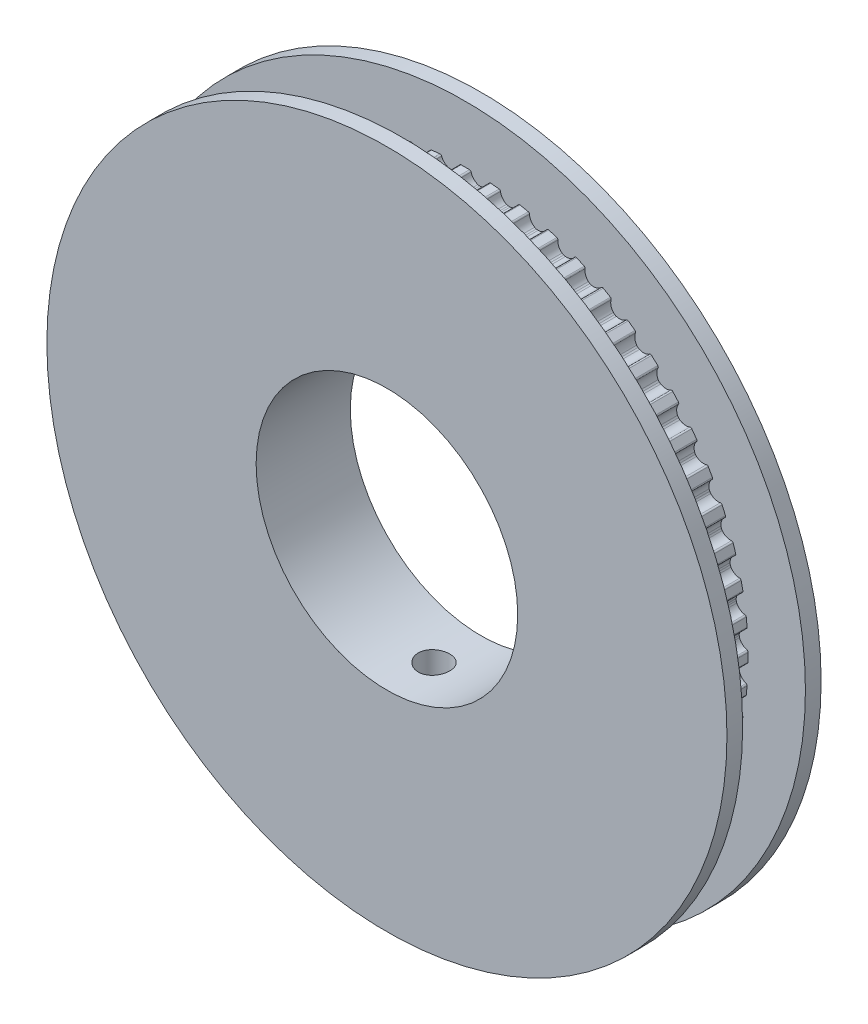
SolidWorks part; units mm, degrees
ref_plane "Front Plane" through (0, 0, 0) normal (0, 0, 1) x (1, 0, 0)
ref_plane "Top Plane" through (0, 0, 0) normal (0, 1, 0) x (1, 0, 0)
ref_plane "Right Plane" through (0, 0, 0) normal (1, 0, 0) x (0, 0, -1)
sketch "Sketch2" plane through (0, 0, 0) normal (0, 0, 1) x (1, 0, 0)
  circle A0 centre (0, 0) radius 27.693
  dimension "D1" = 55.3859
extrude "Boss-Extrude1" add sketch "Sketch2" along normal mid plane 6
sketch "Sketch3" plane through (0, 0, 3) normal (0, 0, 1) x (1, 0, 0)
  line L0 (0, 0) -> (0, 27.0327) construction
  line L1 (0, 27.0327) -> (0.4, 27.0327)
  line L4 (0, 0) -> (1.4605, 27.8689) construction
  line L8 (0, 27.0327) -> (0, 27.8689)
  line L9 (0, 27.8689) -> (1.4605, 27.8689)
  line L10 (2.9131, 27.7163) -> (1.4605, 27.8689)
  line L11 (2.8257, 26.8846) -> (2.4279, 26.9264)
  line L12 (2.8257, 26.8846) -> (2.9131, 27.7163)
  line L13 (5.7943, 27.2599) -> (4.3656, 27.5636)
  line L14 (2.9131, 27.7163) -> (4.3656, 27.5636)
  line L15 (2.8257, 26.8846) -> (2.9131, 27.7163)
  line L16 (2.8257, 26.8846) -> (3.2235, 26.8428)
  line L17 (5.6204, 26.442) -> (5.2292, 26.5251)
  line L18 (5.6204, 26.442) -> (5.7943, 27.2599)
  line L19 (8.612, 26.5049) -> (7.2229, 26.9563)
  line L20 (5.7943, 27.2599) -> (7.2229, 26.9563)
  line L21 (5.6204, 26.442) -> (5.7943, 27.2599)
  line L22 (5.6204, 26.442) -> (6.0117, 26.3588)
  line L23 (8.3536, 25.7096) -> (7.9731, 25.8332)
  line L24 (8.3536, 25.7096) -> (8.612, 26.5049)
  line L25 (11.3353, 25.4595) -> (10.001, 26.0536)
  line L26 (8.612, 26.5049) -> (10.001, 26.0536)
  line L27 (8.3536, 25.7096) -> (8.612, 26.5049)
  line L28 (8.3536, 25.7096) -> (8.734, 25.586)
  line L29 (10.9952, 24.6956) -> (10.6298, 24.8583)
  line L30 (10.9952, 24.6956) -> (11.3353, 25.4595)
  line L31 (13.9345, 24.1352) -> (12.6696, 24.8655)
  line L32 (11.3353, 25.4595) -> (12.6696, 24.8655)
  line L33 (10.9952, 24.6956) -> (11.3353, 25.4595)
  line L34 (10.9952, 24.6956) -> (11.3606, 24.5329)
  line L35 (13.5164, 23.411) -> (13.1699, 23.611)
  line L36 (13.5164, 23.411) -> (13.9345, 24.1352)
  line L37 (16.381, 22.5465) -> (15.1993, 23.4049)
  line L38 (13.9345, 24.1352) -> (15.1993, 23.4049)
  line L39 (13.5164, 23.411) -> (13.9345, 24.1352)
  line L40 (13.5164, 23.411) -> (13.8628, 23.211)
  line L41 (15.8894, 21.8699) -> (15.5658, 22.105)
  line L42 (15.8894, 21.8699) -> (16.381, 22.5465)
  line L43 (18.648, 20.7107) -> (17.5626, 21.688)
  line L44 (16.381, 22.5465) -> (17.5626, 21.688)
  line L45 (15.8894, 21.8699) -> (16.381, 22.5465)
  line L46 (15.8894, 21.8699) -> (16.213, 21.6348)
  line L47 (18.0884, 20.0892) -> (17.7911, 20.3569)
  line L48 (18.0884, 20.0892) -> (18.648, 20.7107)
  line L49 (20.7107, 18.648) -> (19.7334, 19.7334)
  line L50 (18.648, 20.7107) -> (19.7334, 19.7334)
  line L51 (18.0884, 20.0892) -> (18.648, 20.7107)
  line L52 (18.0884, 20.0892) -> (18.3857, 19.8216)
  line L53 (20.0892, 18.0884) -> (19.8216, 18.3857)
  line L54 (20.0892, 18.0884) -> (20.7107, 18.648)
  line L55 (22.5465, 16.381) -> (21.688, 17.5626)
  line L56 (20.7107, 18.648) -> (21.688, 17.5626)
  line L57 (20.0892, 18.0884) -> (20.7107, 18.648)
  line L58 (20.0892, 18.0884) -> (20.3569, 17.7911)
  line L59 (21.8699, 15.8894) -> (21.6348, 16.213)
  line L60 (21.8699, 15.8894) -> (22.5465, 16.381)
  line L61 (24.1352, 13.9345) -> (23.4049, 15.1993)
  line L62 (22.5465, 16.381) -> (23.4049, 15.1993)
  line L63 (21.8699, 15.8894) -> (22.5465, 16.381)
  line L64 (21.8699, 15.8894) -> (22.105, 15.5658)
  line L65 (23.411, 13.5164) -> (23.211, 13.8628)
  line L66 (23.411, 13.5164) -> (24.1352, 13.9345)
  line L67 (25.4595, 11.3353) -> (24.8655, 12.6696)
  line L68 (24.1352, 13.9345) -> (24.8655, 12.6696)
  line L69 (23.411, 13.5164) -> (24.1352, 13.9345)
  line L70 (23.411, 13.5164) -> (23.611, 13.1699)
  line L71 (24.6956, 10.9952) -> (24.5329, 11.3606)
  line L72 (24.6956, 10.9952) -> (25.4595, 11.3353)
  line L73 (26.5049, 8.612) -> (26.0536, 10.001)
  line L74 (25.4595, 11.3353) -> (26.0536, 10.001)
  line L75 (24.6956, 10.9952) -> (25.4595, 11.3353)
  line L76 (24.6956, 10.9952) -> (24.8583, 10.6298)
  line L77 (25.7096, 8.3536) -> (25.586, 8.734)
  line L78 (25.7096, 8.3536) -> (26.5049, 8.612)
  line L79 (27.2599, 5.7943) -> (26.9563, 7.2229)
  line L80 (26.5049, 8.612) -> (26.9563, 7.2229)
  line L81 (25.7096, 8.3536) -> (26.5049, 8.612)
  line L82 (25.7096, 8.3536) -> (25.8332, 7.9731)
  line L83 (26.442, 5.6204) -> (26.3588, 6.0117)
  line L84 (26.442, 5.6204) -> (27.2599, 5.7943)
  line L85 (27.7163, 2.9131) -> (27.5636, 4.3656)
  line L86 (27.2599, 5.7943) -> (27.5636, 4.3656)
  line L87 (26.442, 5.6204) -> (27.2599, 5.7943)
  line L88 (26.442, 5.6204) -> (26.5251, 5.2292)
  line L89 (26.8846, 2.8257) -> (26.8428, 3.2235)
  line L90 (26.8846, 2.8257) -> (27.7163, 2.9131)
  line L91 (27.8689, 0) -> (27.8689, 1.4605)
  line L92 (27.7163, 2.9131) -> (27.8689, 1.4605)
  line L93 (26.8846, 2.8257) -> (27.7163, 2.9131)
  line L94 (26.8846, 2.8257) -> (26.9264, 2.4279)
  line L95 (27.0327, 0) -> (27.0327, 0.4)
  line L96 (27.0327, 0) -> (27.8689, 0)
  line L97 (27.7163, -2.9131) -> (27.8689, -1.4605)
  line L98 (27.8689, 0) -> (27.8689, -1.4605)
  line L99 (27.0327, 0) -> (27.8689, 0)
  line L100 (27.0327, 0) -> (27.0327, -0.4)
  line L101 (26.8846, -2.8257) -> (26.9264, -2.4279)
  line L102 (26.8846, -2.8257) -> (27.7163, -2.9131)
  line L103 (27.2599, -5.7943) -> (27.5636, -4.3656)
  line L104 (27.7163, -2.9131) -> (27.5636, -4.3656)
  line L105 (26.8846, -2.8257) -> (27.7163, -2.9131)
  line L106 (26.8846, -2.8257) -> (26.8428, -3.2235)
  line L107 (26.442, -5.6204) -> (26.5251, -5.2292)
  line L108 (26.442, -5.6204) -> (27.2599, -5.7943)
  line L109 (26.5049, -8.612) -> (26.9563, -7.2229)
  line L110 (27.2599, -5.7943) -> (26.9563, -7.2229)
  line L111 (26.442, -5.6204) -> (27.2599, -5.7943)
  line L112 (26.442, -5.6204) -> (26.3588, -6.0117)
  line L113 (25.7096, -8.3536) -> (25.8332, -7.9731)
  line L114 (25.7096, -8.3536) -> (26.5049, -8.612)
  line L115 (25.4595, -11.3353) -> (26.0536, -10.001)
  line L116 (26.5049, -8.612) -> (26.0536, -10.001)
  line L117 (25.7096, -8.3536) -> (26.5049, -8.612)
  line L118 (25.7096, -8.3536) -> (25.586, -8.734)
  line L119 (24.6956, -10.9952) -> (24.8583, -10.6298)
  line L120 (24.6956, -10.9952) -> (25.4595, -11.3353)
  line L121 (24.1352, -13.9345) -> (24.8655, -12.6696)
  line L122 (25.4595, -11.3353) -> (24.8655, -12.6696)
  line L123 (24.6956, -10.9952) -> (25.4595, -11.3353)
  line L124 (24.6956, -10.9952) -> (24.5329, -11.3606)
  line L125 (23.411, -13.5164) -> (23.611, -13.1699)
  line L126 (23.411, -13.5164) -> (24.1352, -13.9345)
  line L127 (22.5465, -16.381) -> (23.4049, -15.1993)
  line L128 (24.1352, -13.9345) -> (23.4049, -15.1993)
  line L129 (23.411, -13.5164) -> (24.1352, -13.9345)
  line L130 (23.411, -13.5164) -> (23.211, -13.8628)
  line L131 (21.8699, -15.8894) -> (22.105, -15.5658)
  line L132 (21.8699, -15.8894) -> (22.5465, -16.381)
  line L133 (20.7107, -18.648) -> (21.688, -17.5626)
  line L134 (22.5465, -16.381) -> (21.688, -17.5626)
  line L135 (21.8699, -15.8894) -> (22.5465, -16.381)
  line L136 (21.8699, -15.8894) -> (21.6348, -16.213)
  line L137 (20.0892, -18.0884) -> (20.3569, -17.7911)
  line L138 (20.0892, -18.0884) -> (20.7107, -18.648)
  line L139 (18.648, -20.7107) -> (19.7334, -19.7334)
  line L140 (20.7107, -18.648) -> (19.7334, -19.7334)
  line L141 (20.0892, -18.0884) -> (20.7107, -18.648)
  line L142 (20.0892, -18.0884) -> (19.8216, -18.3857)
  line L143 (18.0884, -20.0892) -> (18.3857, -19.8216)
  line L144 (18.0884, -20.0892) -> (18.648, -20.7107)
  line L145 (16.381, -22.5465) -> (17.5626, -21.688)
  line L146 (18.648, -20.7107) -> (17.5626, -21.688)
  line L147 (18.0884, -20.0892) -> (18.648, -20.7107)
  line L148 (18.0884, -20.0892) -> (17.7911, -20.3569)
  line L149 (15.8894, -21.8699) -> (16.213, -21.6348)
  line L150 (15.8894, -21.8699) -> (16.381, -22.5465)
  line L151 (13.9345, -24.1352) -> (15.1993, -23.4049)
  line L152 (16.381, -22.5465) -> (15.1993, -23.4049)
  line L153 (15.8894, -21.8699) -> (16.381, -22.5465)
  line L154 (15.8894, -21.8699) -> (15.5658, -22.105)
  line L155 (13.5164, -23.411) -> (13.8628, -23.211)
  line L156 (13.5164, -23.411) -> (13.9345, -24.1352)
  line L157 (11.3353, -25.4595) -> (12.6696, -24.8655)
  line L158 (13.9345, -24.1352) -> (12.6696, -24.8655)
  line L159 (13.5164, -23.411) -> (13.9345, -24.1352)
  line L160 (13.5164, -23.411) -> (13.1699, -23.611)
  line L161 (10.9952, -24.6956) -> (11.3606, -24.5329)
  line L162 (10.9952, -24.6956) -> (11.3353, -25.4595)
  line L163 (8.612, -26.5049) -> (10.001, -26.0536)
  line L164 (11.3353, -25.4595) -> (10.001, -26.0536)
  line L165 (10.9952, -24.6956) -> (11.3353, -25.4595)
  line L166 (10.9952, -24.6956) -> (10.6298, -24.8583)
  line L167 (8.3536, -25.7096) -> (8.734, -25.586)
  line L168 (8.3536, -25.7096) -> (8.612, -26.5049)
  line L169 (5.7943, -27.2599) -> (7.2229, -26.9563)
  line L170 (8.612, -26.5049) -> (7.2229, -26.9563)
  line L171 (8.3536, -25.7096) -> (8.612, -26.5049)
  line L172 (8.3536, -25.7096) -> (7.9731, -25.8332)
  line L173 (5.6204, -26.442) -> (6.0117, -26.3588)
  line L174 (5.6204, -26.442) -> (5.7943, -27.2599)
  line L175 (2.9131, -27.7163) -> (4.3656, -27.5636)
  line L176 (5.7943, -27.2599) -> (4.3656, -27.5636)
  line L177 (5.6204, -26.442) -> (5.7943, -27.2599)
  line L178 (5.6204, -26.442) -> (5.2292, -26.5251)
  line L179 (2.8257, -26.8846) -> (3.2235, -26.8428)
  line L180 (2.8257, -26.8846) -> (2.9131, -27.7163)
  line L181 (0, -27.8689) -> (1.4605, -27.8689)
  line L182 (2.9131, -27.7163) -> (1.4605, -27.8689)
  line L183 (2.8257, -26.8846) -> (2.9131, -27.7163)
  line L184 (2.8257, -26.8846) -> (2.4279, -26.9264)
  line L185 (0, -27.0327) -> (0.4, -27.0327)
  line L186 (0, -27.0327) -> (0, -27.8689)
  line L187 (-2.9131, -27.7163) -> (-1.4605, -27.8689)
  line L188 (0, -27.8689) -> (-1.4605, -27.8689)
  line L189 (0, -27.0327) -> (0, -27.8689)
  line L190 (0, -27.0327) -> (-0.4, -27.0327)
  line L191 (-2.8257, -26.8846) -> (-2.4279, -26.9264)
  line L192 (-2.8257, -26.8846) -> (-2.9131, -27.7163)
  line L193 (-5.7943, -27.2599) -> (-4.3656, -27.5636)
  line L194 (-2.9131, -27.7163) -> (-4.3656, -27.5636)
  line L195 (-2.8257, -26.8846) -> (-2.9131, -27.7163)
  line L196 (-2.8257, -26.8846) -> (-3.2235, -26.8428)
  line L197 (-5.6204, -26.442) -> (-5.2292, -26.5251)
  line L198 (-5.6204, -26.442) -> (-5.7943, -27.2599)
  line L199 (-8.612, -26.5049) -> (-7.2229, -26.9563)
  line L200 (-5.7943, -27.2599) -> (-7.2229, -26.9563)
  line L201 (-5.6204, -26.442) -> (-5.7943, -27.2599)
  line L202 (-5.6204, -26.442) -> (-6.0117, -26.3588)
  line L203 (-8.3536, -25.7096) -> (-7.9731, -25.8332)
  line L204 (-8.3536, -25.7096) -> (-8.612, -26.5049)
  line L205 (-11.3353, -25.4595) -> (-10.001, -26.0536)
  line L206 (-8.612, -26.5049) -> (-10.001, -26.0536)
  line L207 (-8.3536, -25.7096) -> (-8.612, -26.5049)
  line L208 (-8.3536, -25.7096) -> (-8.734, -25.586)
  line L209 (-10.9952, -24.6956) -> (-10.6298, -24.8583)
  line L210 (-10.9952, -24.6956) -> (-11.3353, -25.4595)
  line L211 (-13.9345, -24.1352) -> (-12.6696, -24.8655)
  line L212 (-11.3353, -25.4595) -> (-12.6696, -24.8655)
  line L213 (-10.9952, -24.6956) -> (-11.3353, -25.4595)
  line L214 (-10.9952, -24.6956) -> (-11.3606, -24.5329)
  line L215 (-13.5164, -23.411) -> (-13.1699, -23.611)
  line L216 (-13.5164, -23.411) -> (-13.9345, -24.1352)
  line L217 (-16.381, -22.5465) -> (-15.1993, -23.4049)
  line L218 (-13.9345, -24.1352) -> (-15.1993, -23.4049)
  line L219 (-13.5164, -23.411) -> (-13.9345, -24.1352)
  line L220 (-13.5164, -23.411) -> (-13.8628, -23.211)
  line L221 (-15.8894, -21.8699) -> (-15.5658, -22.105)
  line L222 (-15.8894, -21.8699) -> (-16.381, -22.5465)
  line L223 (-18.648, -20.7107) -> (-17.5626, -21.688)
  line L224 (-16.381, -22.5465) -> (-17.5626, -21.688)
  line L225 (-15.8894, -21.8699) -> (-16.381, -22.5465)
  line L226 (-15.8894, -21.8699) -> (-16.213, -21.6348)
  line L227 (-18.0884, -20.0892) -> (-17.7911, -20.3569)
  line L228 (-18.0884, -20.0892) -> (-18.648, -20.7107)
  line L229 (-20.7107, -18.648) -> (-19.7334, -19.7334)
  line L230 (-18.648, -20.7107) -> (-19.7334, -19.7334)
  line L231 (-18.0884, -20.0892) -> (-18.648, -20.7107)
  line L232 (-18.0884, -20.0892) -> (-18.3857, -19.8216)
  line L233 (-20.0892, -18.0884) -> (-19.8216, -18.3857)
  line L234 (-20.0892, -18.0884) -> (-20.7107, -18.648)
  line L235 (-22.5465, -16.381) -> (-21.688, -17.5626)
  line L236 (-20.7107, -18.648) -> (-21.688, -17.5626)
  line L237 (-20.0892, -18.0884) -> (-20.7107, -18.648)
  line L238 (-20.0892, -18.0884) -> (-20.3569, -17.7911)
  line L239 (-21.8699, -15.8894) -> (-21.6348, -16.213)
  line L240 (-21.8699, -15.8894) -> (-22.5465, -16.381)
  line L241 (-24.1352, -13.9345) -> (-23.4049, -15.1993)
  line L242 (-22.5465, -16.381) -> (-23.4049, -15.1993)
  line L243 (-21.8699, -15.8894) -> (-22.5465, -16.381)
  line L244 (-21.8699, -15.8894) -> (-22.105, -15.5658)
  line L245 (-23.411, -13.5164) -> (-23.211, -13.8628)
  line L246 (-23.411, -13.5164) -> (-24.1352, -13.9345)
  line L247 (-25.4595, -11.3353) -> (-24.8655, -12.6696)
  line L248 (-24.1352, -13.9345) -> (-24.8655, -12.6696)
  line L249 (-23.411, -13.5164) -> (-24.1352, -13.9345)
  line L250 (-23.411, -13.5164) -> (-23.611, -13.1699)
  line L251 (-24.6956, -10.9952) -> (-24.5329, -11.3606)
  line L252 (-24.6956, -10.9952) -> (-25.4595, -11.3353)
  line L253 (-26.5049, -8.612) -> (-26.0536, -10.001)
  line L254 (-25.4595, -11.3353) -> (-26.0536, -10.001)
  line L255 (-24.6956, -10.9952) -> (-25.4595, -11.3353)
  line L256 (-24.6956, -10.9952) -> (-24.8583, -10.6298)
  line L257 (-25.7096, -8.3536) -> (-25.586, -8.734)
  line L258 (-25.7096, -8.3536) -> (-26.5049, -8.612)
  line L259 (-27.2599, -5.7943) -> (-26.9563, -7.2229)
  line L260 (-26.5049, -8.612) -> (-26.9563, -7.2229)
  line L261 (-25.7096, -8.3536) -> (-26.5049, -8.612)
  line L262 (-25.7096, -8.3536) -> (-25.8332, -7.9731)
  line L263 (-26.442, -5.6204) -> (-26.3588, -6.0117)
  line L264 (-26.442, -5.6204) -> (-27.2599, -5.7943)
  line L265 (-27.7163, -2.9131) -> (-27.5636, -4.3656)
  line L266 (-27.2599, -5.7943) -> (-27.5636, -4.3656)
  line L267 (-26.442, -5.6204) -> (-27.2599, -5.7943)
  line L268 (-26.442, -5.6204) -> (-26.5251, -5.2292)
  line L269 (-26.8846, -2.8257) -> (-26.8428, -3.2235)
  line L270 (-26.8846, -2.8257) -> (-27.7163, -2.9131)
  line L271 (-27.8689, 0) -> (-27.8689, -1.4605)
  line L272 (-27.7163, -2.9131) -> (-27.8689, -1.4605)
  line L273 (-26.8846, -2.8257) -> (-27.7163, -2.9131)
  line L274 (-26.8846, -2.8257) -> (-26.9264, -2.4279)
  line L275 (-27.0327, 0) -> (-27.0327, -0.4)
  line L276 (-27.0327, 0) -> (-27.8689, 0)
  line L277 (-27.7163, 2.9131) -> (-27.8689, 1.4605)
  line L278 (-27.8689, 0) -> (-27.8689, 1.4605)
  line L279 (-27.0327, 0) -> (-27.8689, 0)
  line L280 (-27.0327, 0) -> (-27.0327, 0.4)
  line L281 (-26.8846, 2.8257) -> (-26.9264, 2.4279)
  line L282 (-26.8846, 2.8257) -> (-27.7163, 2.9131)
  line L283 (-27.2599, 5.7943) -> (-27.5636, 4.3656)
  line L284 (-27.7163, 2.9131) -> (-27.5636, 4.3656)
  line L285 (-26.8846, 2.8257) -> (-27.7163, 2.9131)
  line L286 (-26.8846, 2.8257) -> (-26.8428, 3.2235)
  line L287 (-26.442, 5.6204) -> (-26.5251, 5.2292)
  line L288 (-26.442, 5.6204) -> (-27.2599, 5.7943)
  line L289 (-26.5049, 8.612) -> (-26.9563, 7.2229)
  line L290 (-27.2599, 5.7943) -> (-26.9563, 7.2229)
  line L291 (-26.442, 5.6204) -> (-27.2599, 5.7943)
  line L292 (-26.442, 5.6204) -> (-26.3588, 6.0117)
  line L293 (-25.7096, 8.3536) -> (-25.8332, 7.9731)
  line L294 (-25.7096, 8.3536) -> (-26.5049, 8.612)
  line L295 (-25.4595, 11.3353) -> (-26.0536, 10.001)
  line L296 (-26.5049, 8.612) -> (-26.0536, 10.001)
  line L297 (-25.7096, 8.3536) -> (-26.5049, 8.612)
  line L298 (-25.7096, 8.3536) -> (-25.586, 8.734)
  line L299 (-24.6956, 10.9952) -> (-24.8583, 10.6298)
  line L300 (-24.6956, 10.9952) -> (-25.4595, 11.3353)
  line L301 (-24.1352, 13.9345) -> (-24.8655, 12.6696)
  line L302 (-25.4595, 11.3353) -> (-24.8655, 12.6696)
  line L303 (-24.6956, 10.9952) -> (-25.4595, 11.3353)
  line L304 (-24.6956, 10.9952) -> (-24.5329, 11.3606)
  line L305 (-23.411, 13.5164) -> (-23.611, 13.1699)
  line L306 (-23.411, 13.5164) -> (-24.1352, 13.9345)
  line L307 (-22.5465, 16.381) -> (-23.4049, 15.1993)
  line L308 (-24.1352, 13.9345) -> (-23.4049, 15.1993)
  line L309 (-23.411, 13.5164) -> (-24.1352, 13.9345)
  line L310 (-23.411, 13.5164) -> (-23.211, 13.8628)
  line L311 (-21.8699, 15.8894) -> (-22.105, 15.5658)
  line L312 (-21.8699, 15.8894) -> (-22.5465, 16.381)
  line L313 (-20.7107, 18.648) -> (-21.688, 17.5626)
  line L314 (-22.5465, 16.381) -> (-21.688, 17.5626)
  line L315 (-21.8699, 15.8894) -> (-22.5465, 16.381)
  line L316 (-21.8699, 15.8894) -> (-21.6348, 16.213)
  line L317 (-20.0892, 18.0884) -> (-20.3569, 17.7911)
  line L318 (-20.0892, 18.0884) -> (-20.7107, 18.648)
  line L319 (-18.648, 20.7107) -> (-19.7334, 19.7334)
  line L320 (-20.7107, 18.648) -> (-19.7334, 19.7334)
  line L321 (-20.0892, 18.0884) -> (-20.7107, 18.648)
  line L322 (-20.0892, 18.0884) -> (-19.8216, 18.3857)
  line L323 (-18.0884, 20.0892) -> (-18.3857, 19.8216)
  line L324 (-18.0884, 20.0892) -> (-18.648, 20.7107)
  line L325 (-16.381, 22.5465) -> (-17.5626, 21.688)
  line L326 (-18.648, 20.7107) -> (-17.5626, 21.688)
  line L327 (-18.0884, 20.0892) -> (-18.648, 20.7107)
  line L328 (-18.0884, 20.0892) -> (-17.7911, 20.3569)
  line L329 (-15.8894, 21.8699) -> (-16.213, 21.6348)
  line L330 (-15.8894, 21.8699) -> (-16.381, 22.5465)
  line L331 (-13.9345, 24.1352) -> (-15.1993, 23.4049)
  line L332 (-16.381, 22.5465) -> (-15.1993, 23.4049)
  line L333 (-15.8894, 21.8699) -> (-16.381, 22.5465)
  line L334 (-15.8894, 21.8699) -> (-15.5658, 22.105)
  line L335 (-13.5164, 23.411) -> (-13.8628, 23.211)
  line L336 (-13.5164, 23.411) -> (-13.9345, 24.1352)
  line L337 (-11.3353, 25.4595) -> (-12.6696, 24.8655)
  line L338 (-13.9345, 24.1352) -> (-12.6696, 24.8655)
  line L339 (-13.5164, 23.411) -> (-13.9345, 24.1352)
  line L340 (-13.5164, 23.411) -> (-13.1699, 23.611)
  line L341 (-10.9952, 24.6956) -> (-11.3606, 24.5329)
  line L342 (-10.9952, 24.6956) -> (-11.3353, 25.4595)
  line L343 (-8.612, 26.5049) -> (-10.001, 26.0536)
  line L344 (-11.3353, 25.4595) -> (-10.001, 26.0536)
  line L345 (-10.9952, 24.6956) -> (-11.3353, 25.4595)
  line L346 (-10.9952, 24.6956) -> (-10.6298, 24.8583)
  line L347 (-8.3536, 25.7096) -> (-8.734, 25.586)
  line L348 (-8.3536, 25.7096) -> (-8.612, 26.5049)
  line L349 (-5.7943, 27.2599) -> (-7.2229, 26.9563)
  line L350 (-8.612, 26.5049) -> (-7.2229, 26.9563)
  line L351 (-8.3536, 25.7096) -> (-8.612, 26.5049)
  line L352 (-8.3536, 25.7096) -> (-7.9731, 25.8332)
  line L353 (-5.6204, 26.442) -> (-6.0117, 26.3588)
  line L354 (-5.6204, 26.442) -> (-5.7943, 27.2599)
  line L355 (-2.9131, 27.7163) -> (-4.3656, 27.5636)
  line L356 (-5.7943, 27.2599) -> (-4.3656, 27.5636)
  line L357 (-5.6204, 26.442) -> (-5.7943, 27.2599)
  line L358 (-5.6204, 26.442) -> (-5.2292, 26.5251)
  line L359 (-2.8257, 26.8846) -> (-3.2235, 26.8428)
  line L360 (-2.8257, 26.8846) -> (-2.9131, 27.7163)
  line L361 (0, 27.8689) -> (-1.4605, 27.8689)
  line L362 (-2.9131, 27.7163) -> (-1.4605, 27.8689)
  line L363 (-2.8257, 26.8846) -> (-2.9131, 27.7163)
  line L364 (-2.8257, 26.8846) -> (-2.4279, 26.9264)
  line L365 (0, 27.0327) -> (-0.4, 27.0327)
  line L366 (0, 27.0327) -> (0, 27.8689)
  arc A0 (0.4, 27.0327) -> (0.5459, 26.9176) centre (0.4, 26.8827) cw
  arc A1 (0.5459, 26.9176) -> (1.1992, 26.2023) centre (1.5185, 27.1499) ccw
  arc A2 (1.1992, 26.2023) -> (1.3717, 26.1737) centre (1.3749, 26.7287) ccw
  arc A3 (3.2235, 26.8428) -> (3.3566, 26.713) centre (3.2078, 26.6936) cw
  arc A4 (1.5463, 26.1841) -> (1.3717, 26.1737) centre (1.4265, 26.726) cw
  arc A5 (2.2707, 26.8272) -> (1.5463, 26.1841) centre (1.3277, 27.1599) cw
  arc A6 (2.4279, 26.9264) -> (2.2707, 26.8272) centre (2.4122, 26.7772) ccw
  arc A7 (3.3566, 26.713) -> (3.9315, 25.9334) centre (4.3481, 26.8425) ccw
  arc A8 (3.9315, 25.9334) -> (4.1001, 25.887) centre (4.1613, 26.4386) ccw
  arc A9 (4.2748, 25.879) -> (4.1001, 25.887) centre (4.2123, 26.4305) cw
  arc A10 (5.0625, 26.4428) -> (4.2748, 25.879) centre (4.1595, 26.8724) cw
  arc A11 (5.2292, 26.5251) -> (5.0625, 26.4428) centre (5.198, 26.3784) ccw
  arc A12 (6.0117, 26.3588) -> (6.1304, 26.2158) centre (5.9805, 26.2121) cw
  arc A13 (6.1304, 26.2158) -> (6.6207, 25.3804) centre (7.1301, 26.2409) ccw
  arc A14 (6.6207, 25.3804) -> (6.7836, 25.3166) centre (6.9021, 25.8588) ccw
  arc A15 (6.9565, 25.2904) -> (6.7836, 25.3166) centre (6.952, 25.8454) cw
  arc A16 (7.7988, 25.7688) -> (6.9565, 25.2904) centre (6.9456, 26.2904) cw
  arc A17 (7.9731, 25.8332) -> (7.7988, 25.7688) centre (7.9268, 25.6906) ccw
  arc A18 (8.734, 25.586) -> (8.8372, 25.4314) centre (8.6876, 25.4434) cw
  arc A19 (8.8372, 25.4314) -> (9.2374, 24.5493) centre (9.834, 25.3519) ccw
  arc A20 (9.2374, 24.5493) -> (9.3927, 24.4688) centre (9.5673, 24.9957) ccw
  arc A21 (9.562, 24.4247) -> (9.3927, 24.4688) centre (9.6155, 24.9771) cw
  arc A22 (10.4497, 24.8124) -> (9.562, 24.4247) centre (9.6556, 25.4203) cw
  arc A23 (10.6298, 24.8583) -> (10.4497, 24.8124) centre (10.5688, 24.7213) ccw
  arc A24 (11.3606, 24.5329) -> (11.4471, 24.3684) centre (11.2996, 24.3959) cw
  arc A25 (11.4471, 24.3684) -> (11.7529, 23.4493) centre (12.4301, 24.1851) ccw
  arc A26 (11.7529, 23.4493) -> (11.8989, 23.353) centre (12.1276, 23.8587) ccw
  arc A27 (12.0627, 23.2914) -> (11.8989, 23.353) centre (12.1736, 23.8352) cw
  arc A28 (12.986, 23.5842) -> (12.0627, 23.2914) centre (12.2599, 24.2718) cw
  arc A29 (13.1699, 23.611) -> (12.986, 23.5842) centre (13.0949, 23.4811) ccw
  arc A30 (13.8628, 23.211) -> (13.9315, 23.0383) centre (13.7878, 23.0811) cw
  arc A31 (13.9315, 23.0383) -> (14.1396, 22.0923) centre (14.89, 22.7533) ccw
  arc A32 (14.1396, 22.0923) -> (14.2748, 21.9813) centre (14.5551, 22.4603) ccw
  arc A33 (14.4312, 21.903) -> (14.2748, 21.9813) centre (14.5984, 22.4322) cw
  arc A34 (15.3801, 22.0976) -> (14.4312, 21.903) centre (14.7298, 22.8573) cw
  arc A35 (15.5658, 22.105) -> (15.3801, 22.0976) centre (15.4776, 21.9837) ccw
  arc A36 (16.213, 21.6348) -> (16.2634, 21.4559) centre (16.1249, 21.5134) cw
  arc A37 (16.2634, 21.4559) -> (16.3715, 20.4933) centre (17.1868, 21.0722) ccw
  arc A38 (16.3715, 20.4933) -> (16.4943, 20.3687) centre (16.8231, 20.8158) ccw
  arc A39 (16.6416, 20.2745) -> (16.4943, 20.3687) centre (16.8632, 20.7833) cw
  arc A40 (17.6057, 20.3689) -> (16.6416, 20.2745) centre (17.0384, 21.1924) cw
  arc A41 (17.7911, 20.3569) -> (17.6057, 20.3689) centre (17.6908, 20.2454) ccw
  arc A42 (18.3857, 19.8216) -> (18.417, 19.6384) centre (18.2853, 19.7101) cw
  arc A43 (18.417, 19.6384) -> (18.4239, 18.6697) centre (19.2953, 19.1602) ccw
  arc A44 (18.4239, 18.6697) -> (18.533, 18.533) centre (18.9068, 18.9433) ccw
  arc A45 (18.6697, 18.4239) -> (18.533, 18.533) centre (18.9433, 18.9068) cw
  arc A46 (19.6384, 18.417) -> (18.6697, 18.4239) centre (19.1602, 19.2953) cw
  arc A47 (19.8216, 18.3857) -> (19.6384, 18.417) centre (19.7101, 18.2853) ccw
  arc A48 (20.3569, 17.7911) -> (20.3689, 17.6057) centre (20.2454, 17.6908) cw
  arc A49 (20.3689, 17.6057) -> (20.2745, 16.6416) centre (21.1924, 17.0384) ccw
  arc A50 (20.2745, 16.6416) -> (20.3687, 16.4943) centre (20.7833, 16.8632) ccw
  arc A51 (20.4933, 16.3715) -> (20.3687, 16.4943) centre (20.8158, 16.8231) cw
  arc A52 (21.4559, 16.2634) -> (20.4933, 16.3715) centre (21.0722, 17.1868) cw
  arc A53 (21.6348, 16.213) -> (21.4559, 16.2634) centre (21.5134, 16.1249) ccw
  arc A54 (22.105, 15.5658) -> (22.0976, 15.3801) centre (21.9837, 15.4776) cw
  arc A55 (22.0976, 15.3801) -> (21.903, 14.4312) centre (22.8573, 14.7298) ccw
  arc A56 (21.903, 14.4312) -> (21.9813, 14.2748) centre (22.4322, 14.5984) ccw
  arc A57 (22.0923, 14.1396) -> (21.9813, 14.2748) centre (22.4603, 14.5551) cw
  arc A58 (23.0383, 13.9315) -> (22.0923, 14.1396) centre (22.7533, 14.89) cw
  arc A59 (23.211, 13.8628) -> (23.0383, 13.9315) centre (23.0811, 13.7878) ccw
  arc A60 (23.611, 13.1699) -> (23.5842, 12.986) centre (23.4811, 13.0949) cw
  arc A61 (23.5842, 12.986) -> (23.2914, 12.0627) centre (24.2718, 12.2599) ccw
  arc A62 (23.2914, 12.0627) -> (23.353, 11.8989) centre (23.8352, 12.1736) ccw
  arc A63 (23.4493, 11.7529) -> (23.353, 11.8989) centre (23.8587, 12.1276) cw
  arc A64 (24.3684, 11.4471) -> (23.4493, 11.7529) centre (24.1851, 12.4301) cw
  arc A65 (24.5329, 11.3606) -> (24.3684, 11.4471) centre (24.3959, 11.2996) ccw
  arc A66 (24.8583, 10.6298) -> (24.8124, 10.4497) centre (24.7213, 10.5688) cw
  arc A67 (24.8124, 10.4497) -> (24.4247, 9.562) centre (25.4203, 9.6556) ccw
  arc A68 (24.4247, 9.562) -> (24.4688, 9.3927) centre (24.9771, 9.6155) ccw
  arc A69 (24.5493, 9.2374) -> (24.4688, 9.3927) centre (24.9957, 9.5673) cw
  arc A70 (25.4314, 8.8372) -> (24.5493, 9.2374) centre (25.3519, 9.834) cw
  arc A71 (25.586, 8.734) -> (25.4314, 8.8372) centre (25.4434, 8.6876) ccw
  arc A72 (25.8332, 7.9731) -> (25.7688, 7.7988) centre (25.6906, 7.9268) cw
  arc A73 (25.7688, 7.7988) -> (25.2904, 6.9565) centre (26.2904, 6.9456) ccw
  arc A74 (25.2904, 6.9565) -> (25.3166, 6.7836) centre (25.8454, 6.952) ccw
  arc A75 (25.3804, 6.6207) -> (25.3166, 6.7836) centre (25.8588, 6.9021) cw
  arc A76 (26.2158, 6.1304) -> (25.3804, 6.6207) centre (26.2409, 7.1301) cw
  arc A77 (26.3588, 6.0117) -> (26.2158, 6.1304) centre (26.2121, 5.9805) ccw
  arc A78 (26.5251, 5.2292) -> (26.4428, 5.0625) centre (26.3784, 5.198) cw
  arc A79 (26.4428, 5.0625) -> (25.879, 4.2748) centre (26.8724, 4.1595) ccw
  arc A80 (25.879, 4.2748) -> (25.887, 4.1001) centre (26.4305, 4.2123) ccw
  arc A81 (25.9334, 3.9315) -> (25.887, 4.1001) centre (26.4386, 4.1613) cw
  arc A82 (26.713, 3.3566) -> (25.9334, 3.9315) centre (26.8425, 4.3481) cw
  arc A83 (26.8428, 3.2235) -> (26.713, 3.3566) centre (26.6936, 3.2078) ccw
  arc A84 (26.9264, 2.4279) -> (26.8272, 2.2707) centre (26.7772, 2.4122) cw
  arc A85 (26.8272, 2.2707) -> (26.1841, 1.5463) centre (27.1599, 1.3277) ccw
  arc A86 (26.1841, 1.5463) -> (26.1737, 1.3717) centre (26.726, 1.4265) ccw
  arc A87 (26.2023, 1.1992) -> (26.1737, 1.3717) centre (26.7287, 1.3749) cw
  arc A88 (26.9176, 0.5459) -> (26.2023, 1.1992) centre (27.1499, 1.5185) cw
  arc A89 (27.0327, 0.4) -> (26.9176, 0.5459) centre (26.8827, 0.4) ccw
  arc A90 (27.0327, -0.4) -> (26.9176, -0.5459) centre (26.8827, -0.4) cw
  arc A91 (26.9176, -0.5459) -> (26.2023, -1.1992) centre (27.1499, -1.5185) ccw
  arc A92 (26.2023, -1.1992) -> (26.1737, -1.3717) centre (26.7287, -1.3749) ccw
  arc A93 (26.1841, -1.5463) -> (26.1737, -1.3717) centre (26.726, -1.4265) cw
  arc A94 (26.8272, -2.2707) -> (26.1841, -1.5463) centre (27.1599, -1.3277) cw
  arc A95 (26.9264, -2.4279) -> (26.8272, -2.2707) centre (26.7772, -2.4122) ccw
  arc A96 (26.8428, -3.2235) -> (26.713, -3.3566) centre (26.6936, -3.2078) cw
  arc A97 (26.713, -3.3566) -> (25.9334, -3.9315) centre (26.8425, -4.3481) ccw
  arc A98 (25.9334, -3.9315) -> (25.887, -4.1001) centre (26.4386, -4.1613) ccw
  arc A99 (25.879, -4.2748) -> (25.887, -4.1001) centre (26.4305, -4.2123) cw
  arc A100 (26.4428, -5.0625) -> (25.879, -4.2748) centre (26.8724, -4.1595) cw
  arc A101 (26.5251, -5.2292) -> (26.4428, -5.0625) centre (26.3784, -5.198) ccw
  arc A102 (26.3588, -6.0117) -> (26.2158, -6.1304) centre (26.2121, -5.9805) cw
  arc A103 (26.2158, -6.1304) -> (25.3804, -6.6207) centre (26.2409, -7.1301) ccw
  arc A104 (25.3804, -6.6207) -> (25.3166, -6.7836) centre (25.8588, -6.9021) ccw
  arc A105 (25.2904, -6.9565) -> (25.3166, -6.7836) centre (25.8454, -6.952) cw
  arc A106 (25.7688, -7.7988) -> (25.2904, -6.9565) centre (26.2904, -6.9456) cw
  arc A107 (25.8332, -7.9731) -> (25.7688, -7.7988) centre (25.6906, -7.9268) ccw
  arc A108 (25.586, -8.734) -> (25.4314, -8.8372) centre (25.4434, -8.6876) cw
  arc A109 (25.4314, -8.8372) -> (24.5493, -9.2374) centre (25.3519, -9.834) ccw
  arc A110 (24.5493, -9.2374) -> (24.4688, -9.3927) centre (24.9957, -9.5673) ccw
  arc A111 (24.4247, -9.562) -> (24.4688, -9.3927) centre (24.9771, -9.6155) cw
  arc A112 (24.8124, -10.4497) -> (24.4247, -9.562) centre (25.4203, -9.6556) cw
  arc A113 (24.8583, -10.6298) -> (24.8124, -10.4497) centre (24.7213, -10.5688) ccw
  arc A114 (24.5329, -11.3606) -> (24.3684, -11.4471) centre (24.3959, -11.2996) cw
  arc A115 (24.3684, -11.4471) -> (23.4493, -11.7529) centre (24.1851, -12.4301) ccw
  arc A116 (23.4493, -11.7529) -> (23.353, -11.8989) centre (23.8587, -12.1276) ccw
  arc A117 (23.2914, -12.0627) -> (23.353, -11.8989) centre (23.8352, -12.1736) cw
  arc A118 (23.5842, -12.986) -> (23.2914, -12.0627) centre (24.2718, -12.2599) cw
  arc A119 (23.611, -13.1699) -> (23.5842, -12.986) centre (23.4811, -13.0949) ccw
  arc A120 (23.211, -13.8628) -> (23.0383, -13.9315) centre (23.0811, -13.7878) cw
  arc A121 (23.0383, -13.9315) -> (22.0923, -14.1396) centre (22.7533, -14.89) ccw
  arc A122 (22.0923, -14.1396) -> (21.9813, -14.2748) centre (22.4603, -14.5551) ccw
  arc A123 (21.903, -14.4312) -> (21.9813, -14.2748) centre (22.4322, -14.5984) cw
  arc A124 (22.0976, -15.3801) -> (21.903, -14.4312) centre (22.8573, -14.7298) cw
  arc A125 (22.105, -15.5658) -> (22.0976, -15.3801) centre (21.9837, -15.4776) ccw
  arc A126 (21.6348, -16.213) -> (21.4559, -16.2634) centre (21.5134, -16.1249) cw
  arc A127 (21.4559, -16.2634) -> (20.4933, -16.3715) centre (21.0722, -17.1868) ccw
  arc A128 (20.4933, -16.3715) -> (20.3687, -16.4943) centre (20.8158, -16.8231) ccw
  arc A129 (20.2745, -16.6416) -> (20.3687, -16.4943) centre (20.7833, -16.8632) cw
  arc A130 (20.3689, -17.6057) -> (20.2745, -16.6416) centre (21.1924, -17.0384) cw
  arc A131 (20.3569, -17.7911) -> (20.3689, -17.6057) centre (20.2454, -17.6908) ccw
  arc A132 (19.8216, -18.3857) -> (19.6384, -18.417) centre (19.7101, -18.2853) cw
  arc A133 (19.6384, -18.417) -> (18.6697, -18.4239) centre (19.1602, -19.2953) ccw
  arc A134 (18.6697, -18.4239) -> (18.533, -18.533) centre (18.9433, -18.9068) ccw
  arc A135 (18.4239, -18.6697) -> (18.533, -18.533) centre (18.9068, -18.9433) cw
  arc A136 (18.417, -19.6384) -> (18.4239, -18.6697) centre (19.2953, -19.1602) cw
  arc A137 (18.3857, -19.8216) -> (18.417, -19.6384) centre (18.2853, -19.7101) ccw
  arc A138 (17.7911, -20.3569) -> (17.6057, -20.3689) centre (17.6908, -20.2454) cw
  arc A139 (17.6057, -20.3689) -> (16.6416, -20.2745) centre (17.0384, -21.1924) ccw
  arc A140 (16.6416, -20.2745) -> (16.4943, -20.3687) centre (16.8632, -20.7833) ccw
  arc A141 (16.3715, -20.4933) -> (16.4943, -20.3687) centre (16.8231, -20.8158) cw
  arc A142 (16.2634, -21.4559) -> (16.3715, -20.4933) centre (17.1868, -21.0722) cw
  arc A143 (16.213, -21.6348) -> (16.2634, -21.4559) centre (16.1249, -21.5134) ccw
  arc A144 (15.5658, -22.105) -> (15.3801, -22.0976) centre (15.4776, -21.9837) cw
  arc A145 (15.3801, -22.0976) -> (14.4312, -21.903) centre (14.7298, -22.8573) ccw
  arc A146 (14.4312, -21.903) -> (14.2748, -21.9813) centre (14.5984, -22.4322) ccw
  arc A147 (14.1396, -22.0923) -> (14.2748, -21.9813) centre (14.5551, -22.4603) cw
  arc A148 (13.9315, -23.0383) -> (14.1396, -22.0923) centre (14.89, -22.7533) cw
  arc A149 (13.8628, -23.211) -> (13.9315, -23.0383) centre (13.7878, -23.0811) ccw
  arc A150 (13.1699, -23.611) -> (12.986, -23.5842) centre (13.0949, -23.4811) cw
  arc A151 (12.986, -23.5842) -> (12.0627, -23.2914) centre (12.2599, -24.2718) ccw
  arc A152 (12.0627, -23.2914) -> (11.8989, -23.353) centre (12.1736, -23.8352) ccw
  arc A153 (11.7529, -23.4493) -> (11.8989, -23.353) centre (12.1276, -23.8587) cw
  arc A154 (11.4471, -24.3684) -> (11.7529, -23.4493) centre (12.4301, -24.1851) cw
  arc A155 (11.3606, -24.5329) -> (11.4471, -24.3684) centre (11.2996, -24.3959) ccw
  arc A156 (10.6298, -24.8583) -> (10.4497, -24.8124) centre (10.5688, -24.7213) cw
  arc A157 (10.4497, -24.8124) -> (9.562, -24.4247) centre (9.6556, -25.4203) ccw
  arc A158 (9.562, -24.4247) -> (9.3927, -24.4688) centre (9.6155, -24.9771) ccw
  arc A159 (9.2374, -24.5493) -> (9.3927, -24.4688) centre (9.5673, -24.9957) cw
  arc A160 (8.8372, -25.4314) -> (9.2374, -24.5493) centre (9.834, -25.3519) cw
  arc A161 (8.734, -25.586) -> (8.8372, -25.4314) centre (8.6876, -25.4434) ccw
  arc A162 (7.9731, -25.8332) -> (7.7988, -25.7688) centre (7.9268, -25.6906) cw
  arc A163 (7.7988, -25.7688) -> (6.9565, -25.2904) centre (6.9456, -26.2904) ccw
  arc A164 (6.9565, -25.2904) -> (6.7836, -25.3166) centre (6.952, -25.8454) ccw
  arc A165 (6.6207, -25.3804) -> (6.7836, -25.3166) centre (6.9021, -25.8588) cw
  arc A166 (6.1304, -26.2158) -> (6.6207, -25.3804) centre (7.1301, -26.2409) cw
  arc A167 (6.0117, -26.3588) -> (6.1304, -26.2158) centre (5.9805, -26.2121) ccw
  arc A168 (5.2292, -26.5251) -> (5.0625, -26.4428) centre (5.198, -26.3784) cw
  arc A169 (5.0625, -26.4428) -> (4.2748, -25.879) centre (4.1595, -26.8724) ccw
  arc A170 (4.2748, -25.879) -> (4.1001, -25.887) centre (4.2123, -26.4305) ccw
  arc A171 (3.9315, -25.9334) -> (4.1001, -25.887) centre (4.1613, -26.4386) cw
  arc A172 (3.3566, -26.713) -> (3.9315, -25.9334) centre (4.3481, -26.8425) cw
  arc A173 (3.2235, -26.8428) -> (3.3566, -26.713) centre (3.2078, -26.6936) ccw
  arc A174 (2.4279, -26.9264) -> (2.2707, -26.8272) centre (2.4122, -26.7772) cw
  arc A175 (2.2707, -26.8272) -> (1.5463, -26.1841) centre (1.3277, -27.1599) ccw
  arc A176 (1.5463, -26.1841) -> (1.3717, -26.1737) centre (1.4265, -26.726) ccw
  arc A177 (1.1992, -26.2023) -> (1.3717, -26.1737) centre (1.3749, -26.7287) cw
  arc A178 (0.5459, -26.9176) -> (1.1992, -26.2023) centre (1.5185, -27.1499) cw
  arc A179 (0.4, -27.0327) -> (0.5459, -26.9176) centre (0.4, -26.8827) ccw
  arc A180 (-0.4, -27.0327) -> (-0.5459, -26.9176) centre (-0.4, -26.8827) cw
  arc A181 (-0.5459, -26.9176) -> (-1.1992, -26.2023) centre (-1.5185, -27.1499) ccw
  arc A182 (-1.1992, -26.2023) -> (-1.3717, -26.1737) centre (-1.3749, -26.7287) ccw
  arc A183 (-1.5463, -26.1841) -> (-1.3717, -26.1737) centre (-1.4265, -26.726) cw
  arc A184 (-2.2707, -26.8272) -> (-1.5463, -26.1841) centre (-1.3277, -27.1599) cw
  arc A185 (-2.4279, -26.9264) -> (-2.2707, -26.8272) centre (-2.4122, -26.7772) ccw
  arc A186 (-3.2235, -26.8428) -> (-3.3566, -26.713) centre (-3.2078, -26.6936) cw
  arc A187 (-3.3566, -26.713) -> (-3.9315, -25.9334) centre (-4.3481, -26.8425) ccw
  arc A188 (-3.9315, -25.9334) -> (-4.1001, -25.887) centre (-4.1613, -26.4386) ccw
  arc A189 (-4.2748, -25.879) -> (-4.1001, -25.887) centre (-4.2123, -26.4305) cw
  arc A190 (-5.0625, -26.4428) -> (-4.2748, -25.879) centre (-4.1595, -26.8724) cw
  arc A191 (-5.2292, -26.5251) -> (-5.0625, -26.4428) centre (-5.198, -26.3784) ccw
  arc A192 (-6.0117, -26.3588) -> (-6.1304, -26.2158) centre (-5.9805, -26.2121) cw
  arc A193 (-6.1304, -26.2158) -> (-6.6207, -25.3804) centre (-7.1301, -26.2409) ccw
  arc A194 (-6.6207, -25.3804) -> (-6.7836, -25.3166) centre (-6.9021, -25.8588) ccw
  arc A195 (-6.9565, -25.2904) -> (-6.7836, -25.3166) centre (-6.952, -25.8454) cw
  arc A196 (-7.7988, -25.7688) -> (-6.9565, -25.2904) centre (-6.9456, -26.2904) cw
  arc A197 (-7.9731, -25.8332) -> (-7.7988, -25.7688) centre (-7.9268, -25.6906) ccw
  arc A198 (-8.734, -25.586) -> (-8.8372, -25.4314) centre (-8.6876, -25.4434) cw
  arc A199 (-8.8372, -25.4314) -> (-9.2374, -24.5493) centre (-9.834, -25.3519) ccw
  arc A200 (-9.2374, -24.5493) -> (-9.3927, -24.4688) centre (-9.5673, -24.9957) ccw
  arc A201 (-9.562, -24.4247) -> (-9.3927, -24.4688) centre (-9.6155, -24.9771) cw
  arc A202 (-10.4497, -24.8124) -> (-9.562, -24.4247) centre (-9.6556, -25.4203) cw
  arc A203 (-10.6298, -24.8583) -> (-10.4497, -24.8124) centre (-10.5688, -24.7213) ccw
  arc A204 (-11.3606, -24.5329) -> (-11.4471, -24.3684) centre (-11.2996, -24.3959) cw
  arc A205 (-11.4471, -24.3684) -> (-11.7529, -23.4493) centre (-12.4301, -24.1851) ccw
  arc A206 (-11.7529, -23.4493) -> (-11.8989, -23.353) centre (-12.1276, -23.8587) ccw
  arc A207 (-12.0627, -23.2914) -> (-11.8989, -23.353) centre (-12.1736, -23.8352) cw
  arc A208 (-12.986, -23.5842) -> (-12.0627, -23.2914) centre (-12.2599, -24.2718) cw
  arc A209 (-13.1699, -23.611) -> (-12.986, -23.5842) centre (-13.0949, -23.4811) ccw
  arc A210 (-13.8628, -23.211) -> (-13.9315, -23.0383) centre (-13.7878, -23.0811) cw
  arc A211 (-13.9315, -23.0383) -> (-14.1396, -22.0923) centre (-14.89, -22.7533) ccw
  arc A212 (-14.1396, -22.0923) -> (-14.2748, -21.9813) centre (-14.5551, -22.4603) ccw
  arc A213 (-14.4312, -21.903) -> (-14.2748, -21.9813) centre (-14.5984, -22.4322) cw
  arc A214 (-15.3801, -22.0976) -> (-14.4312, -21.903) centre (-14.7298, -22.8573) cw
  arc A215 (-15.5658, -22.105) -> (-15.3801, -22.0976) centre (-15.4776, -21.9837) ccw
  arc A216 (-16.213, -21.6348) -> (-16.2634, -21.4559) centre (-16.1249, -21.5134) cw
  arc A217 (-16.2634, -21.4559) -> (-16.3715, -20.4933) centre (-17.1868, -21.0722) ccw
  arc A218 (-16.3715, -20.4933) -> (-16.4943, -20.3687) centre (-16.8231, -20.8158) ccw
  arc A219 (-16.6416, -20.2745) -> (-16.4943, -20.3687) centre (-16.8632, -20.7833) cw
  arc A220 (-17.6057, -20.3689) -> (-16.6416, -20.2745) centre (-17.0384, -21.1924) cw
  arc A221 (-17.7911, -20.3569) -> (-17.6057, -20.3689) centre (-17.6908, -20.2454) ccw
  arc A222 (-18.3857, -19.8216) -> (-18.417, -19.6384) centre (-18.2853, -19.7101) cw
  arc A223 (-18.417, -19.6384) -> (-18.4239, -18.6697) centre (-19.2953, -19.1602) ccw
  arc A224 (-18.4239, -18.6697) -> (-18.533, -18.533) centre (-18.9068, -18.9433) ccw
  arc A225 (-18.6697, -18.4239) -> (-18.533, -18.533) centre (-18.9433, -18.9068) cw
  arc A226 (-19.6384, -18.417) -> (-18.6697, -18.4239) centre (-19.1602, -19.2953) cw
  arc A227 (-19.8216, -18.3857) -> (-19.6384, -18.417) centre (-19.7101, -18.2853) ccw
  arc A228 (-20.3569, -17.7911) -> (-20.3689, -17.6057) centre (-20.2454, -17.6908) cw
  arc A229 (-20.3689, -17.6057) -> (-20.2745, -16.6416) centre (-21.1924, -17.0384) ccw
  arc A230 (-20.2745, -16.6416) -> (-20.3687, -16.4943) centre (-20.7833, -16.8632) ccw
  arc A231 (-20.4933, -16.3715) -> (-20.3687, -16.4943) centre (-20.8158, -16.8231) cw
  arc A232 (-21.4559, -16.2634) -> (-20.4933, -16.3715) centre (-21.0722, -17.1868) cw
  arc A233 (-21.6348, -16.213) -> (-21.4559, -16.2634) centre (-21.5134, -16.1249) ccw
  arc A234 (-22.105, -15.5658) -> (-22.0976, -15.3801) centre (-21.9837, -15.4776) cw
  arc A235 (-22.0976, -15.3801) -> (-21.903, -14.4312) centre (-22.8573, -14.7298) ccw
  arc A236 (-21.903, -14.4312) -> (-21.9813, -14.2748) centre (-22.4322, -14.5984) ccw
  arc A237 (-22.0923, -14.1396) -> (-21.9813, -14.2748) centre (-22.4603, -14.5551) cw
  arc A238 (-23.0383, -13.9315) -> (-22.0923, -14.1396) centre (-22.7533, -14.89) cw
  arc A239 (-23.211, -13.8628) -> (-23.0383, -13.9315) centre (-23.0811, -13.7878) ccw
  arc A240 (-23.611, -13.1699) -> (-23.5842, -12.986) centre (-23.4811, -13.0949) cw
  arc A241 (-23.5842, -12.986) -> (-23.2914, -12.0627) centre (-24.2718, -12.2599) ccw
  arc A242 (-23.2914, -12.0627) -> (-23.353, -11.8989) centre (-23.8352, -12.1736) ccw
  arc A243 (-23.4493, -11.7529) -> (-23.353, -11.8989) centre (-23.8587, -12.1276) cw
  arc A244 (-24.3684, -11.4471) -> (-23.4493, -11.7529) centre (-24.1851, -12.4301) cw
  arc A245 (-24.5329, -11.3606) -> (-24.3684, -11.4471) centre (-24.3959, -11.2996) ccw
  arc A246 (-24.8583, -10.6298) -> (-24.8124, -10.4497) centre (-24.7213, -10.5688) cw
  arc A247 (-24.8124, -10.4497) -> (-24.4247, -9.562) centre (-25.4203, -9.6556) ccw
  arc A248 (-24.4247, -9.562) -> (-24.4688, -9.3927) centre (-24.9771, -9.6155) ccw
  arc A249 (-24.5493, -9.2374) -> (-24.4688, -9.3927) centre (-24.9957, -9.5673) cw
  arc A250 (-25.4314, -8.8372) -> (-24.5493, -9.2374) centre (-25.3519, -9.834) cw
  arc A251 (-25.586, -8.734) -> (-25.4314, -8.8372) centre (-25.4434, -8.6876) ccw
  arc A252 (-25.8332, -7.9731) -> (-25.7688, -7.7988) centre (-25.6906, -7.9268) cw
  arc A253 (-25.7688, -7.7988) -> (-25.2904, -6.9565) centre (-26.2904, -6.9456) ccw
  arc A254 (-25.2904, -6.9565) -> (-25.3166, -6.7836) centre (-25.8454, -6.952) ccw
  arc A255 (-25.3804, -6.6207) -> (-25.3166, -6.7836) centre (-25.8588, -6.9021) cw
  arc A256 (-26.2158, -6.1304) -> (-25.3804, -6.6207) centre (-26.2409, -7.1301) cw
  arc A257 (-26.3588, -6.0117) -> (-26.2158, -6.1304) centre (-26.2121, -5.9805) ccw
  arc A258 (-26.5251, -5.2292) -> (-26.4428, -5.0625) centre (-26.3784, -5.198) cw
  arc A259 (-26.4428, -5.0625) -> (-25.879, -4.2748) centre (-26.8724, -4.1595) ccw
  arc A260 (-25.879, -4.2748) -> (-25.887, -4.1001) centre (-26.4305, -4.2123) ccw
  arc A261 (-25.9334, -3.9315) -> (-25.887, -4.1001) centre (-26.4386, -4.1613) cw
  arc A262 (-26.713, -3.3566) -> (-25.9334, -3.9315) centre (-26.8425, -4.3481) cw
  arc A263 (-26.8428, -3.2235) -> (-26.713, -3.3566) centre (-26.6936, -3.2078) ccw
  arc A264 (-26.9264, -2.4279) -> (-26.8272, -2.2707) centre (-26.7772, -2.4122) cw
  arc A265 (-26.8272, -2.2707) -> (-26.1841, -1.5463) centre (-27.1599, -1.3277) ccw
  arc A266 (-26.1841, -1.5463) -> (-26.1737, -1.3717) centre (-26.726, -1.4265) ccw
  arc A267 (-26.2023, -1.1992) -> (-26.1737, -1.3717) centre (-26.7287, -1.3749) cw
  arc A268 (-26.9176, -0.5459) -> (-26.2023, -1.1992) centre (-27.1499, -1.5185) cw
  arc A269 (-27.0327, -0.4) -> (-26.9176, -0.5459) centre (-26.8827, -0.4) ccw
  arc A270 (-27.0327, 0.4) -> (-26.9176, 0.5459) centre (-26.8827, 0.4) cw
  arc A271 (-26.9176, 0.5459) -> (-26.2023, 1.1992) centre (-27.1499, 1.5185) ccw
  arc A272 (-26.2023, 1.1992) -> (-26.1737, 1.3717) centre (-26.7287, 1.3749) ccw
  arc A273 (-26.1841, 1.5463) -> (-26.1737, 1.3717) centre (-26.726, 1.4265) cw
  arc A274 (-26.8272, 2.2707) -> (-26.1841, 1.5463) centre (-27.1599, 1.3277) cw
  arc A275 (-26.9264, 2.4279) -> (-26.8272, 2.2707) centre (-26.7772, 2.4122) ccw
  arc A276 (-26.8428, 3.2235) -> (-26.713, 3.3566) centre (-26.6936, 3.2078) cw
  arc A277 (-26.713, 3.3566) -> (-25.9334, 3.9315) centre (-26.8425, 4.3481) ccw
  arc A278 (-25.9334, 3.9315) -> (-25.887, 4.1001) centre (-26.4386, 4.1613) ccw
  arc A279 (-25.879, 4.2748) -> (-25.887, 4.1001) centre (-26.4305, 4.2123) cw
  arc A280 (-26.4428, 5.0625) -> (-25.879, 4.2748) centre (-26.8724, 4.1595) cw
  arc A281 (-26.5251, 5.2292) -> (-26.4428, 5.0625) centre (-26.3784, 5.198) ccw
  arc A282 (-26.3588, 6.0117) -> (-26.2158, 6.1304) centre (-26.2121, 5.9805) cw
  arc A283 (-26.2158, 6.1304) -> (-25.3804, 6.6207) centre (-26.2409, 7.1301) ccw
  arc A284 (-25.3804, 6.6207) -> (-25.3166, 6.7836) centre (-25.8588, 6.9021) ccw
  arc A285 (-25.2904, 6.9565) -> (-25.3166, 6.7836) centre (-25.8454, 6.952) cw
  arc A286 (-25.7688, 7.7988) -> (-25.2904, 6.9565) centre (-26.2904, 6.9456) cw
  arc A287 (-25.8332, 7.9731) -> (-25.7688, 7.7988) centre (-25.6906, 7.9268) ccw
  arc A288 (-25.586, 8.734) -> (-25.4314, 8.8372) centre (-25.4434, 8.6876) cw
  arc A289 (-25.4314, 8.8372) -> (-24.5493, 9.2374) centre (-25.3519, 9.834) ccw
  arc A290 (-24.5493, 9.2374) -> (-24.4688, 9.3927) centre (-24.9957, 9.5673) ccw
  arc A291 (-24.4247, 9.562) -> (-24.4688, 9.3927) centre (-24.9771, 9.6155) cw
  arc A292 (-24.8124, 10.4497) -> (-24.4247, 9.562) centre (-25.4203, 9.6556) cw
  arc A293 (-24.8583, 10.6298) -> (-24.8124, 10.4497) centre (-24.7213, 10.5688) ccw
  arc A294 (-24.5329, 11.3606) -> (-24.3684, 11.4471) centre (-24.3959, 11.2996) cw
  arc A295 (-24.3684, 11.4471) -> (-23.4493, 11.7529) centre (-24.1851, 12.4301) ccw
  arc A296 (-23.4493, 11.7529) -> (-23.353, 11.8989) centre (-23.8587, 12.1276) ccw
  arc A297 (-23.2914, 12.0627) -> (-23.353, 11.8989) centre (-23.8352, 12.1736) cw
  arc A298 (-23.5842, 12.986) -> (-23.2914, 12.0627) centre (-24.2718, 12.2599) cw
  arc A299 (-23.611, 13.1699) -> (-23.5842, 12.986) centre (-23.4811, 13.0949) ccw
  arc A300 (-23.211, 13.8628) -> (-23.0383, 13.9315) centre (-23.0811, 13.7878) cw
  arc A301 (-23.0383, 13.9315) -> (-22.0923, 14.1396) centre (-22.7533, 14.89) ccw
  arc A302 (-22.0923, 14.1396) -> (-21.9813, 14.2748) centre (-22.4603, 14.5551) ccw
  arc A303 (-21.903, 14.4312) -> (-21.9813, 14.2748) centre (-22.4322, 14.5984) cw
  arc A304 (-22.0976, 15.3801) -> (-21.903, 14.4312) centre (-22.8573, 14.7298) cw
  arc A305 (-22.105, 15.5658) -> (-22.0976, 15.3801) centre (-21.9837, 15.4776) ccw
  arc A306 (-21.6348, 16.213) -> (-21.4559, 16.2634) centre (-21.5134, 16.1249) cw
  arc A307 (-21.4559, 16.2634) -> (-20.4933, 16.3715) centre (-21.0722, 17.1868) ccw
  arc A308 (-20.4933, 16.3715) -> (-20.3687, 16.4943) centre (-20.8158, 16.8231) ccw
  arc A309 (-20.2745, 16.6416) -> (-20.3687, 16.4943) centre (-20.7833, 16.8632) cw
  arc A310 (-20.3689, 17.6057) -> (-20.2745, 16.6416) centre (-21.1924, 17.0384) cw
  arc A311 (-20.3569, 17.7911) -> (-20.3689, 17.6057) centre (-20.2454, 17.6908) ccw
  arc A312 (-19.8216, 18.3857) -> (-19.6384, 18.417) centre (-19.7101, 18.2853) cw
  arc A313 (-19.6384, 18.417) -> (-18.6697, 18.4239) centre (-19.1602, 19.2953) ccw
  arc A314 (-18.6697, 18.4239) -> (-18.533, 18.533) centre (-18.9433, 18.9068) ccw
  arc A315 (-18.4239, 18.6697) -> (-18.533, 18.533) centre (-18.9068, 18.9433) cw
  arc A316 (-18.417, 19.6384) -> (-18.4239, 18.6697) centre (-19.2953, 19.1602) cw
  arc A317 (-18.3857, 19.8216) -> (-18.417, 19.6384) centre (-18.2853, 19.7101) ccw
  arc A318 (-17.7911, 20.3569) -> (-17.6057, 20.3689) centre (-17.6908, 20.2454) cw
  arc A319 (-17.6057, 20.3689) -> (-16.6416, 20.2745) centre (-17.0384, 21.1924) ccw
  arc A320 (-16.6416, 20.2745) -> (-16.4943, 20.3687) centre (-16.8632, 20.7833) ccw
  arc A321 (-16.3715, 20.4933) -> (-16.4943, 20.3687) centre (-16.8231, 20.8158) cw
  arc A322 (-16.2634, 21.4559) -> (-16.3715, 20.4933) centre (-17.1868, 21.0722) cw
  arc A323 (-16.213, 21.6348) -> (-16.2634, 21.4559) centre (-16.1249, 21.5134) ccw
  arc A324 (-15.5658, 22.105) -> (-15.3801, 22.0976) centre (-15.4776, 21.9837) cw
  arc A325 (-15.3801, 22.0976) -> (-14.4312, 21.903) centre (-14.7298, 22.8573) ccw
  arc A326 (-14.4312, 21.903) -> (-14.2748, 21.9813) centre (-14.5984, 22.4322) ccw
  arc A327 (-14.1396, 22.0923) -> (-14.2748, 21.9813) centre (-14.5551, 22.4603) cw
  arc A328 (-13.9315, 23.0383) -> (-14.1396, 22.0923) centre (-14.89, 22.7533) cw
  arc A329 (-13.8628, 23.211) -> (-13.9315, 23.0383) centre (-13.7878, 23.0811) ccw
  arc A330 (-13.1699, 23.611) -> (-12.986, 23.5842) centre (-13.0949, 23.4811) cw
  arc A331 (-12.986, 23.5842) -> (-12.0627, 23.2914) centre (-12.2599, 24.2718) ccw
  arc A332 (-12.0627, 23.2914) -> (-11.8989, 23.353) centre (-12.1736, 23.8352) ccw
  arc A333 (-11.7529, 23.4493) -> (-11.8989, 23.353) centre (-12.1276, 23.8587) cw
  arc A334 (-11.4471, 24.3684) -> (-11.7529, 23.4493) centre (-12.4301, 24.1851) cw
  arc A335 (-11.3606, 24.5329) -> (-11.4471, 24.3684) centre (-11.2996, 24.3959) ccw
  arc A336 (-10.6298, 24.8583) -> (-10.4497, 24.8124) centre (-10.5688, 24.7213) cw
  arc A337 (-10.4497, 24.8124) -> (-9.562, 24.4247) centre (-9.6556, 25.4203) ccw
  arc A338 (-9.562, 24.4247) -> (-9.3927, 24.4688) centre (-9.6155, 24.9771) ccw
  arc A339 (-9.2374, 24.5493) -> (-9.3927, 24.4688) centre (-9.5673, 24.9957) cw
  arc A340 (-8.8372, 25.4314) -> (-9.2374, 24.5493) centre (-9.834, 25.3519) cw
  arc A341 (-8.734, 25.586) -> (-8.8372, 25.4314) centre (-8.6876, 25.4434) ccw
  arc A342 (-7.9731, 25.8332) -> (-7.7988, 25.7688) centre (-7.9268, 25.6906) cw
  arc A343 (-7.7988, 25.7688) -> (-6.9565, 25.2904) centre (-6.9456, 26.2904) ccw
  arc A344 (-6.9565, 25.2904) -> (-6.7836, 25.3166) centre (-6.952, 25.8454) ccw
  arc A345 (-6.6207, 25.3804) -> (-6.7836, 25.3166) centre (-6.9021, 25.8588) cw
  arc A346 (-6.1304, 26.2158) -> (-6.6207, 25.3804) centre (-7.1301, 26.2409) cw
  arc A347 (-6.0117, 26.3588) -> (-6.1304, 26.2158) centre (-5.9805, 26.2121) ccw
  arc A348 (-5.2292, 26.5251) -> (-5.0625, 26.4428) centre (-5.198, 26.3784) cw
  arc A349 (-5.0625, 26.4428) -> (-4.2748, 25.879) centre (-4.1595, 26.8724) ccw
  arc A350 (-4.2748, 25.879) -> (-4.1001, 25.887) centre (-4.2123, 26.4305) ccw
  arc A351 (-3.9315, 25.9334) -> (-4.1001, 25.887) centre (-4.1613, 26.4386) cw
  arc A352 (-3.3566, 26.713) -> (-3.9315, 25.9334) centre (-4.3481, 26.8425) cw
  arc A353 (-3.2235, 26.8428) -> (-3.3566, 26.713) centre (-3.2078, 26.6936) ccw
  arc A354 (-2.4279, 26.9264) -> (-2.2707, 26.8272) centre (-2.4122, 26.7772) cw
  arc A355 (-2.2707, 26.8272) -> (-1.5463, 26.1841) centre (-1.3277, 27.1599) ccw
  arc A356 (-1.5463, 26.1841) -> (-1.3717, 26.1737) centre (-1.4265, 26.726) ccw
  arc A357 (-1.1992, 26.2023) -> (-1.3717, 26.1737) centre (-1.3749, 26.7287) cw
  arc A358 (-0.5459, 26.9176) -> (-1.1992, 26.2023) centre (-1.5185, 27.1499) cw
  arc A359 (-0.4, 27.0327) -> (-0.5459, 26.9176) centre (-0.4, 26.8827) ccw
  point P1085 (0, 0)
  circle M1 centre (0, 0) radius 27.693
  dimension "D1" = 0.15
  dimension "D2" = 1
  dimension "D3" = 0.555
  dimension "D7" = 3
  dimension "D8" = 60
  dimension "D4" = 0.4
  dimension "D5" = 0.8362
  dimension "D6" = 1.4605
extrude "Cut-Extrude5" cut sketch "Sketch3" against normal through all contours A341 L347 L348 L345 L346 A336 A337 A338 A339 A340 M1 | A347 L353 L354 L351 L352 A342 A343 A344 A345 A346 M1 | A353 L359 L360 L357 L358 A348 A349 A350 A351 A352 M1 | A359 L365 L366 L363 L364 A354 A355 A356 A357 A358 M1 | A6 L11 L12 L8 L1 A0 A1 A2 A4 A5 M1 | A11 L17 L18 L15 L16 A3 A7 A8 A9 A10 M1 | A17 L23 L24 L21 L22 A12 A13 A14 A15 A16 M1 | A29 L35 L36 L33 L34 A24 A25 A26 A27 A28 M1 | A23 L29 L30 L27 L28 A18 A19 A20 A21 A22 M1 | A35 L41 L42 L39 L40 A30 A31 A32 A33 A34 M1 | A41 L47 L48 L45 L46 A36 A37 A38 A39 A40 M1 | A53 L59 L60 L57 L58 A48 A49 A50 A51 A52 M1 | A47 L53 L54 L51 L52 A42 A43 A44 A45 A46 M1 | A59 L65 L66 L63 L64 A54 A55 A56 A57 A58 M1 | A65 L71 L72 L69 L70 A60 A61 A62 A63 A64 M1 | A71 L77 L78 L75 L76 A66 A67 A68 A69 A70 M1 | A77 L83 L84 L81 L82 A72 A73 A74 A75 A76 M1 | A83 L89 L90 L87 L88 A78 A79 A80 A81 A82 M1 | A335 L341 L342 L339 L340 A330 A331 A332 A333 A334 M1 | A329 L335 L336 L333 L334 A324 A325 A326 A327 A328 M1 | A323 L329 L330 L327 L328 A318 A319 A320 A321 A322 M1 | A299 L305 L306 L303 L304 A294 A295 A296 A297 A298 M1 | A305 L311 L312 L309 L310 A300 A301 A302 A303 A304 M1 | A311 L317 L318 L315 L316 A306 A307 A308 A309 A310 M1 | A317 L323 L324 L321 L322 A312 A313 A314 A315 A316 M1 | A293 L299 L300 L297 L298 A288 A289 A290 A291 A292 M1 | A287 L293 L294 L291 L292 A282 A283 A284 A285 A286 M1 | A281 L287 L288 L285 L286 A276 A277 A278 A279 A280 M1 | A275 L281 L282 L279 L280 A270 A271 A272 A273 A274 M1 | A269 L275 L276 L273 L274 A264 A265 A266 A267 A268 M1 | A263 L269 L270 L267 L268 A258 A259 A260 A261 A262 M1 | A257 L263 L264 L261 L262 A252 A253 A254 A255 A256 M1 | A251 L257 L258 L255 L256 A246 A247 A248 A249 A250 M1 | A89 L95 L96 L93 L94 A84 A85 A86 A87 A88 M1 | A95 L101 L102 L99 L100 A90 A91 A92 A93 A94 M1 | A101 L107 L108 L105 L106 A96 A97 A98 A99 A100 M1 | A107 L113 L114 L111 L112 A102 A103 A104 A105 A106 M1 | A113 L119 L120 L117 L118 A108 A109 A110 A111 A112 M1 | A119 L125 L126 L123 L124 A114 A115 A116 A117 A118 M1 | A125 L131 L132 L129 L130 A120 A121 A122 A123 A124 M1 | A131 L137 L138 L135 L136 A126 A127 A128 A129 A130 M1 | A137 L143 L144 L141 L142 A132 A133 A134 A135 A136 M1 | A143 L149 L150 L147 L148 A138 A139 A140 A141 A142 M1 | A155 L161 L162 L159 L160 A150 A151 A152 A153 A154 M1 | A149 L155 L156 L153 L154 A144 A145 A146 A147 A148 M1 | A161 L167 L168 L165 L166 A156 A157 A158 A159 A160 M1 | A167 L173 L174 L171 L172 A162 A163 A164 A165 A166 M1 | A245 L251 L252 L249 L250 A240 A241 A242 A243 A244 M1 | A239 L245 L246 L243 L244 A234 A235 A236 A237 A238 M1 | A233 L239 L240 L237 L238 A228 A229 A230 A231 A232 M1 | A227 L233 L234 L231 L232 A222 A223 A224 A225 A226 M1 | A221 L227 L228 L225 L226 A216 A217 A218 A219 A220 M1 | A215 L221 L222 L219 L220 A210 A211 A212 A213 A214 M1 | A209 L215 L216 L213 L214 A204 A205 A206 A207 A208 M1 | A203 L209 L210 L207 L208 A198 A199 A200 A201 A202 M1 | A197 L203 L204 L201 L202 A192 A193 A194 A195 A196 M1 | A191 L197 L198 L195 L196 A186 A187 A188 A189 A190 M1 | A185 L191 L192 L189 L190 A180 A181 A182 A183 A184 M1 | A173 L179 L180 L177 L178 A168 A169 A170 A171 A172 M1 | A179 L185 L186 L183 L184 A174 A175 A176 A177 A178 M1 region at (1.4188, 27.0729, 3) region at (-1.4188, 27.0729, 3) region at (4.2409, 26.7762, 3) region at (-4.2409, 26.7762, 3) region at (7.0166, 26.1863, 3) region at (-7.0166, 26.1863, 3) region at (9.7154, 25.3094, 3) region at (-9.7154, 25.3094, 3) region at (12.3077, 24.1552, 3) region at (-12.3077, 24.1552, 3) region at (14.7652, 22.7364, 3) region at (-14.7652, 22.7364, 3) region at (17.0609, 21.0684, 3) region at (-17.0609, 21.0684, 3) region at (19.1697, 19.1697, 3) region at (-19.1697, 19.1697, 3) region at (21.0684, 17.0609, 3) region at (-21.0684, 17.0609, 3) region at (22.7364, 14.7652, 3) region at (-22.7364, 14.7652, 3) region at (24.1552, 12.3077, 3) region at (-24.1552, 12.3077, 3) region at (25.3094, 9.7154, 3) region at (-25.3094, 9.7154, 3) region at (26.1863, 7.0166, 3) region at (-26.1863, 7.0166, 3) region at (26.7762, 4.2409, 3) region at (-26.7762, 4.2409, 3) region at (27.0729, 1.4188, 3) region at (-27.0729, 1.4188, 3) region at (27.0729, -1.4188, 3) region at (-27.0729, -1.4188, 3) region at (26.7762, -4.2409, 3) region at (-26.7762, -4.2409, 3) region at (26.1863, -7.0166, 3) region at (-26.1863, -7.0166, 3) region at (25.3094, -9.7154, 3) region at (-25.3094, -9.7154, 3) region at (24.1552, -12.3077, 3) region at (-24.1552, -12.3077, 3) region at (22.7364, -14.7652, 3) region at (-22.7364, -14.7652, 3) region at (21.0684, -17.0609, 3) region at (-21.0684, -17.0609, 3) region at (19.1697, -19.1697, 3) region at (-19.1697, -19.1697, 3) region at (17.0609, -21.0684, 3) region at (-17.0609, -21.0684, 3) region at (14.7652, -22.7364, 3) region at (-14.7652, -22.7364, 3) region at (12.3077, -24.1552, 3) region at (-12.3077, -24.1552, 3) region at (9.7154, -25.3094, 3) region at (-9.7154, -25.3094, 3) region at (7.0166, -26.1863, 3) region at (-7.0166, -26.1863, 3) region at (4.2409, -26.7762, 3) region at (-4.2409, -26.7762, 3) region at (1.4188, -27.0729, 3) region at (-1.4188, -27.0729, 3)
sketch "Sketch4" plane through (0, 0, 3) normal (0, 0, 1) x (1, 0, 0)
  circle A1 centre (0, 0) radius 32.5
  dimension "D1" = 65
extrude "Boss-Extrude2" add sketch "Sketch4" along normal blind 1.5
sketch "Sketch5" plane through (0, 0, -3) normal (0, 0, -1) x (-1, 0, 0)
  circle A0 centre (0, 0) radius 32.5
  dimension "D1" = 65
extrude "Boss-Extrude3" add sketch "Sketch5" along normal blind 1.5
sketch "Sketch6" plane through (0, 0, 4.5) normal (0, 0, 1) x (1, 0, 0)
  circle A0 centre (0, 0) radius 12.5
  dimension "D1" = 25
extrude "Cut-Extrude6" cut sketch "Sketch6" against normal up to next
sketch "Sketch8" plane through (0, 0, 0) normal (0, 1, 0) x (1, 0, 0)
  circle A0 centre (0, 0) radius 1.5
  dimension "D1" = 3
extrude "Cut-Extrude7" cut sketch "Sketch8" against normal through all
equation "\"n\" = 87"
equation "\"p\"= 2mm"
equation "\"pd\"= \"n\" * \"p\" / pi"
equation "\"D1@Sketch2\"=\"pd\""
